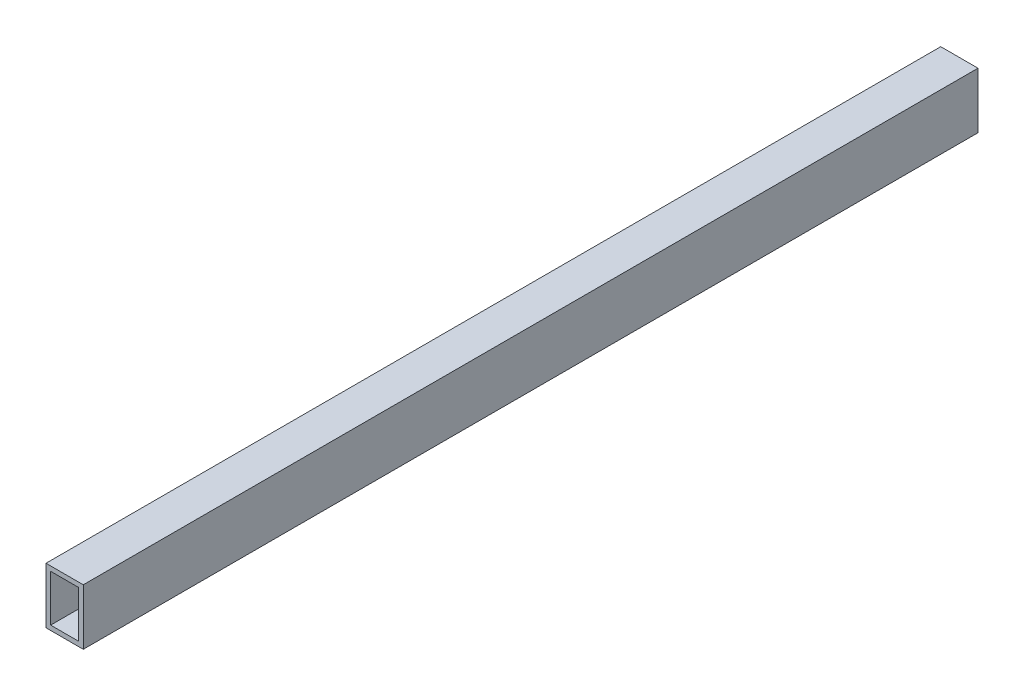
SolidWorks part; units mm, degrees
material "6063-T1"
ref_plane "Front Plane" through (0, 0, 0) normal (0, 0, 1) x (1, 0, 0)
ref_plane "Top Plane" through (0, 0, 0) normal (0, 1, 0) x (1, 0, 0)
ref_plane "Right Plane" through (0, 0, 0) normal (1, 0, 0) x (0, 0, -1)
sketch "Sketch1" plane through (0, 0, 0) normal (0, 0, 1) x (1, 0, 0)
  line L1 (-12.7, 19.05) -> (12.7, 19.05)
  line L2 (-12.7, 19.05) -> (-12.7, -19.05)
  line L3 (-12.7, -19.05) -> (12.7, -19.05)
  line L4 (12.7, 19.05) -> (12.7, -19.05)
  line L5 (-12.7, 19.05) -> (12.7, -19.05) construction
  line L6 (-12.7, -19.05) -> (12.7, 19.05) construction
  point P0 (0, 0)
  dimension "D1" = 25.4
  dimension "D2" = 38.1
extrude "Boss-Extrude1" add sketch "Sketch1" along normal blind 609.6
shell "Shell1" thickness 3.175 removed face at (0, 0, 0) removed face at (0, 0, 609.6)
